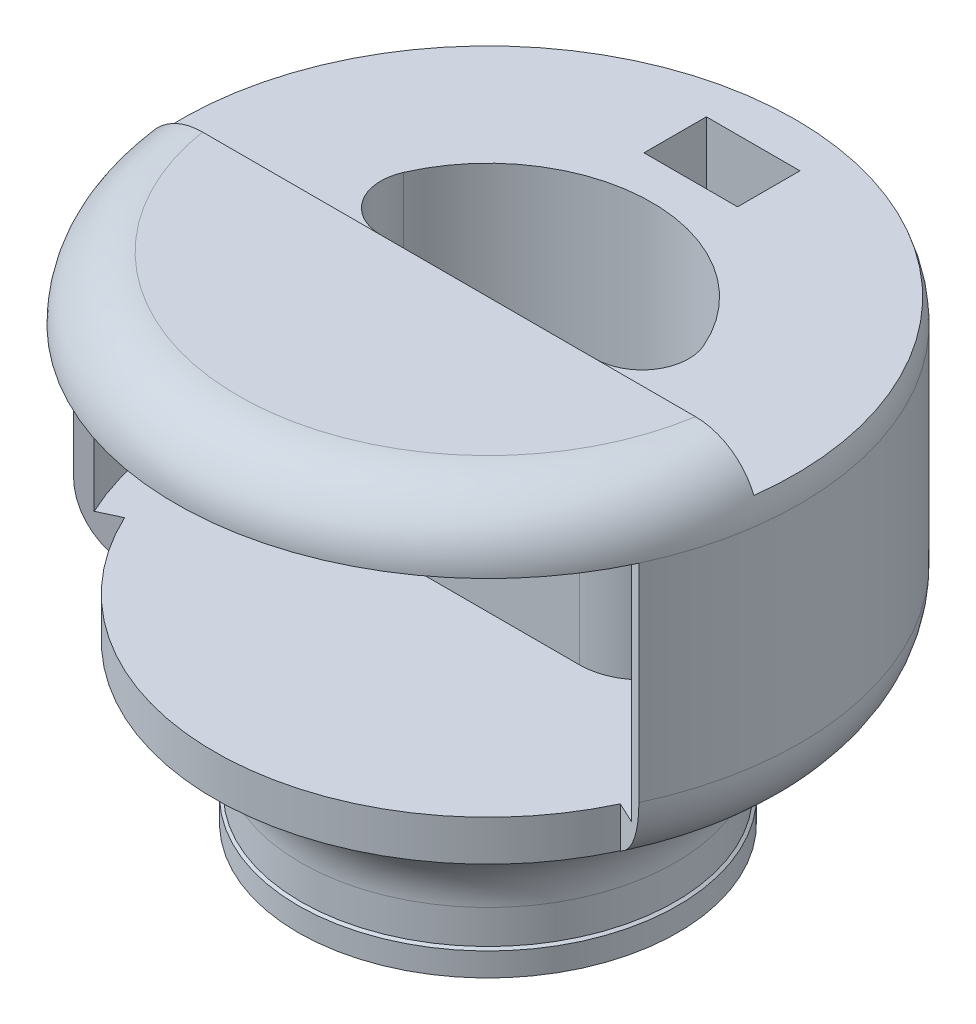
SolidWorks part; units mm, degrees
ref_plane "Front Plane" through (0, 0, 0) normal (0, 0, 1) x (1, 0, 0)
ref_plane "Top Plane" through (0, 0, 0) normal (0, 1, 0) x (1, 0, 0)
ref_plane "Right Plane" through (0, 0, 0) normal (1, 0, 0) x (0, 0, -1)
sketch "Sketch1" plane through (0, 0, 0) normal (0, 0, 1) x (1, 0, 0)
  line L0 (0, 0) -> (0, 90.2242) construction
  line L28 (0, 63.4279) -> (32, 63.4279)
  line L29 (40, 55.4279) -> (40, 28.8468)
  line L30 (22.5, 0) -> (24.35, 0)
  line L31 (24.35, 0) -> (24.35, 3)
  line L32 (24.35, 3) -> (24, 3.25)
  line L33 (24, 3.25) -> (24, 7.5811)
  line L34 (28.5399, 15.9588) -> (35.4601, 20.4691)
  line L35 (0, 13) -> (22, 13)
  line L36 (22.5, 12.5) -> (22.5, 0)
  line L37 (0, 13) -> (0, 63.4279)
  arc A0 (22, 13) -> (22.5, 12.5) centre (22, 12.5) cw
  arc A1 (24, 7.5811) -> (28.5399, 15.9588) centre (34, 7.5811) cw
  arc A2 (35.4601, 20.4691) -> (40, 28.8468) centre (30, 28.8468) ccw
  arc A3 (32, 63.4279) -> (40, 55.4279) centre (32, 55.4279) cw
  point P11 (22.9, 63.4279)
  point P18 (22.5, 13)
  point P21 (24, 13)
  point P24 (40, 23.4279)
  point P27 (40, 63.4279)
  point P28 (28.5604, 23.4279)
  point P31 (22.5, 17)
  dimension "D8" = 9.75
  dimension "D9" = 0.5
  dimension "D4" = 1.85
  dimension "D1" = 22.5
  dimension "D10" = 10
  dimension "D11" = 10
  dimension "D12" = 8
  dimension "D2" = 40
  dimension "D3" = 40
  dimension "D5" = 1.5
  dimension "D6" = 3
  dimension "D7" = 13
revolve "Revolve1" add sketch "Sketch1" angle 360 about L0
ref_plane "Plane1" through (0, 13, 0) normal (0, -1, 0) x (-1, 0, 0)
sketch "Sketch18" plane through (0, 0, 0) normal (0, 0, 1) x (1, 0, 0)
  line L0 (0, 0) -> (0, 101.5813) construction
  line L1 (-24.35, 0) -> (24.35, 0) construction
sketch "Sketch3" plane through (0, 0, 0) normal (0, 0, 1) x (1, 0, 0)
  point P0 (1.2404, 19.1989)
ref_point "Point1"
ref_plane "Plane2" through (0, 0, 22.9) normal (0, 0, 1) x (1, 0, 0)
ref_plane "Plane3" through (0, 0, 40) normal (0, 0, 1) x (1, 0, 0)
ref_plane "Plane4" through (0, 55.4279, 0) normal (0, 1, 0) x (1, 0, 0)
sketch "Sketch9" plane through (0, 55.4279, 0) normal (0, 1, 0) x (1, 0, 0)
  circle A7 centre (0, 0) radius 38
  circle A8 centre (0, 0) radius 40 construction
  circle A9 centre (0, 0) radius 23
  dimension "D1" = 2
  dimension "D2" = 46
ref_plane "Plane5" through (0, 13, 0) normal (0, -1, 0) x (-1, 0, 0)
sketch "Sketch11" plane through (0, 13, 0) normal (0, -1, 0) x (-1, 0, 0)
  line L0 (-21, 0) -> (21, 0)
  arc A1 (-21, 0) -> (21, 0) centre (0, 0) cw
  dimension "D1" = 42
extrude "Cut-Extrude3" cut sketch "Sketch11" against normal blind 60
ref_plane "Plane6" through (0, 0, -40) normal (0, 0, -1) x (-1, 0, 0)
extrude "Cut-Extrude5" cut sketch "Sketch9" against normal blind 30 and the other way blind 2
sketch "Sketch19" plane through (0, 0, 0) normal (1, 0, 0) x (0, 0, -1)
  line L0 (-47.0647, 55.4279) -> (-35.0647, 55.4279)
  line L1 (31.2976, 55.4279) -> (-31.2976, 55.4279) construction
  line L2 (-35.0647, 55.4279) -> (-35.0647, 18.9279)
  line L3 (-35.0647, 18.9279) -> (-47.0647, 18.9279)
  line L4 (-47.0647, 18.9279) -> (-47.0647, 55.4279)
  dimension "D1" = 12
  dimension "D2" = 36.5
revolve "Cut-Revolve2" cut sketch "Sketch19" angle 65 about L0 other way angle 65
ref_plane "Plane7" through (0, 0, 22.5) normal (0, 0, -1) x (-1, 0, 0)
sketch "Sketch21" plane through (0, 0, 22.5) normal (0, 0, -1) x (-1, 0, 0)
  line L0 (0, 0) -> (0, 101.5813) construction
  line L1 (-1.625, 4) -> (1.625, 4)
  line L2 (-1.625, 4) -> (-1.625, 0)
  line L3 (-1.625, 0) -> (1.625, 0)
  line L4 (1.625, 4) -> (1.625, 0)
  line L5 (-1.625, 4) -> (1.625, 0) construction
  line L6 (-1.625, 0) -> (1.625, 4) construction
  line L7 (-22.5, 0) -> (22.5, 0) construction
  point P0 (0, 2)
  dimension "D1" = 4
  dimension "D2" = 3.25
extrude "Boss-Extrude3" add sketch "Sketch21" along normal blind 1.35
pattern_circular "CirPattern1" count 5 over 360 about axis through (0, 0, 0) along (0, -1, 0) of "Boss-Extrude3"
ref_plane "Plane8" through (0, 20.4691, 0) normal (0, 1, 0) x (1, 0, 0)
sketch "Sketch22" plane through (0, 63.4279, 0) normal (0, 1, 0) x (1, 0, 0)
  line L0 (-40, 0) -> (40, 0)
  arc A0 (-40, 0) -> (40, 0) centre (0, 0) cw
  arc A1 (36.2523, -16.9047) -> (-36.2523, -16.9047) centre (0, 0) ccw construction
extrude "Cut-Extrude9" cut sketch "Sketch22" against normal blind 5
sketch "Sketch23" plane through (0, 0, -40) normal (0, 0, -1) x (-1, 0, 0)
  line L0 (0, 0) -> (0, 101.5813) construction
  line L1 (31.2976, 55.4279) -> (-31.2976, 55.4279) construction
  circle A0 centre (0, 42.1379) radius 10.5
  dimension "D1" = 21
  dimension "D2" = 13.29
extrude "Cut-Extrude10" cut sketch "Sketch23" against normal blind 10
sketch "Sketch24" plane through (0, 58.4279, 0) normal (0, 1, 0) x (1, 0, 0)
  line L1 (-8.5, 36) -> (8.5, 36)
  line L2 (-8.5, 36) -> (-8.5, 24)
  line L3 (-8.5, 24) -> (8.5, 24)
  line L4 (8.5, 36) -> (8.5, 24)
  line L5 (-8.5, 36) -> (8.5, 24) construction
  line L6 (-8.5, 24) -> (8.5, 36) construction
  arc A0 (39.4162, 0) -> (-39.4162, 0) centre (0, 0) ccw construction
  point P0 (0, 30)
  dimension "D1" = 30
  dimension "D2" = 12
  dimension "D3" = 17
extrude "Boss-Extrude4" add sketch "Sketch24" against normal blind 8
sketch "Sketch26" plane through (0, 58.4279, 0) normal (0, 1, 0) x (1, 0, 0)
  line L1 (-6, 34) -> (6, 34)
  line L2 (-6, 34) -> (-6, 26)
  line L3 (-6, 26) -> (6, 26)
  line L4 (6, 34) -> (6, 26)
  line L5 (-6, 34) -> (6, 26) construction
  line L6 (-6, 26) -> (6, 34) construction
  arc A0 (39.4162, 0) -> (-39.4162, 0) centre (0, 0) ccw construction
  point P0 (0, 30)
  dimension "D1" = 30
  dimension "D2" = 8
  dimension "D3" = 12
extrude "Cut-Extrude11" cut sketch "Sketch26" against normal blind 10
sketch "Sketch27" plane through (8.5, 0, 0) normal (1, 0, 0) x (0, 0, -1)
  line L0 (36, 50.4279) -> (36, 57.4279) construction
  line L1 (27.5, 56.4279) -> (31.5, 56.4279)
  line L2 (27.5, 56.4279) -> (27.5, 51.4279)
  line L3 (27.5, 51.4279) -> (31.5, 51.4279)
  line L4 (31.5, 56.4279) -> (31.5, 51.4279)
  line L5 (27.5, 56.4279) -> (31.5, 51.4279) construction
  line L6 (27.5, 51.4279) -> (31.5, 56.4279) construction
  line L7 (24, 50.4279) -> (24, 57.4279) construction
  line L8 (24, 50.4279) -> (36, 50.4279) construction
  point P0 (29.5, 53.9279)
  dimension "D1" = 12
  dimension "D2" = 3.5
  dimension "D3" = 5
  dimension "D4" = 4
  dimension "D5" = 5.5
extrude "Cut-Extrude12" cut sketch "Sketch27" against normal blind 5
ref_plane "Plane9" through (-39.4162, 58.4279, 0) normal (0.375, 0.927, 0) x (0.927, -0.375, 0)
ref_plane "Plane10" through (0, 58.4279, 0) normal (0, 1, 0) x (1, 0, 0)
sketch "Sketch28" plane through (0, 55.4279, 0) normal (0, 1, 0) x (1, 0, 0)
  line L0 (-22.9129, -2) -> (22.9129, -2)
  arc A0 (-22.9129, -2) -> (22.9129, -2) centre (0, 0) ccw
  dimension "D1" = 46
  dimension "D2" = 2
extrude "Cut-Extrude14" cut sketch "Sketch28" against normal blind 30 and the other way blind 2
sketch "Sketch29" plane through (0, 0, 0) normal (0, 0, -1) x (-1, 0, 0)
  line L0 (0, 0) -> (0, 101.5813) construction
  line L1 (32, 63.4279) -> (-32, 63.4279) construction
  circle A0 centre (-30.4162, 60.9279) radius 1
  circle A1 centre (30.4162, 60.9279) radius 1
  circle A2 centre (0, 60.9279) radius 1
  dimension "D1" = 2
  dimension "D2" = 2
  dimension "D3" = 2
  dimension "D4" = 2.5
  dimension "D5" = 2.5
  dimension "D6" = 2.5
  dimension "D7" = 9
  dimension "D8" = 9
extrude "Cut-Extrude15" cut sketch "Sketch29" against normal blind 15
fillet "Fillet1" radius 6 2 edges at (-21, 35.7139, 0) (21, 35.7139, 0)
fillet "Fillet2" radius 8 2 edges at (22.9129, 41.4279, 2) (-22.9129, 41.4279, 2)
sketch "Sketch30" plane through (0, 63.4279, 0) normal (0, 1, 0) x (1, 0, 0)
  line L0 (-32, 0) -> (32, 0) construction
  line L1 (-49.3805, 0) -> (48.3231, 0)
  line L2 (-49.3805, 0) -> (-49.3805, -5)
  line L3 (-49.3805, -5) -> (48.3231, -5)
  line L4 (48.3231, 0) -> (48.3231, -5)
  dimension "D1" = 5
  dimension "D2" = 0
extrude "Cut-Extrude16" cut sketch "Sketch30" against normal blind 5
